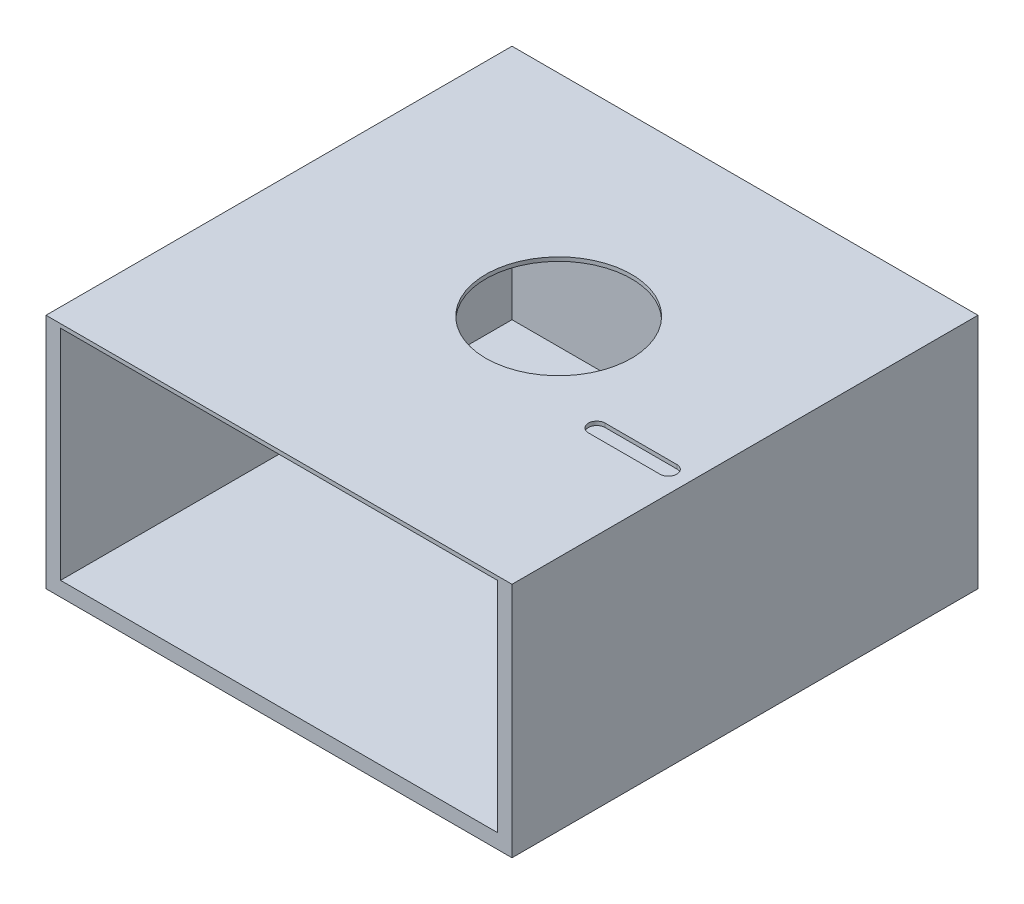
SolidWorks part; units mm, degrees
ref_plane "Front Plane" through (0, 0, 0) normal (0, 0, 1) x (1, 0, 0)
ref_plane "Top Plane" through (0, 0, 0) normal (0, 1, 0) x (1, 0, 0)
ref_plane "Right Plane" through (0, 0, 0) normal (1, 0, 0) x (0, 0, -1)
sketch "Sketch1" plane through (0, 0, 0) normal (0, 0, 1) x (1, 0, 0)
  line L1 (-152.4, -76.2) -> (152.4, -76.2)
  line L2 (-152.4, -76.2) -> (-152.4, 76.2)
  line L3 (-152.4, 76.2) -> (152.4, 76.2)
  line L4 (152.4, -76.2) -> (152.4, 76.2)
  line L5 (-152.4, -76.2) -> (152.4, 76.2) construction
  line L6 (-152.4, 76.2) -> (152.4, -76.2) construction
  point P0 (0, 0)
  dimension "D1" = 304.8
  dimension "D2" = 152.4
extrude "Boss-Extrude1" add sketch "Sketch1" along normal blind 304.8
shell "Shell1" thickness 9.525 removed face at (0, 0, 304.8) removed face at (0, 76.2, 152.4)
sketch "Sketch2" plane through (0, 76.2, 0) normal (0, 1, 0) x (1, 0, 0)
  line L0 (-142.875, -304.8) -> (142.875, -304.8)
  line L8 (-152.4, -304.8) -> (-142.875, -304.8)
  line L9 (-142.875, -304.8) -> (-142.875, -9.525)
  line L10 (-142.875, -9.525) -> (142.875, -9.525)
  line L11 (142.875, -9.525) -> (142.875, -304.8)
  line L12 (142.875, -304.8) -> (152.4, -304.8)
  line L13 (152.4, -304.8) -> (152.4, 0)
  line L14 (152.4, 0) -> (-152.4, 0)
  line L15 (-152.4, 0) -> (-152.4, -304.8)
  line L16 (-152.4, -304.8) -> (-142.875, -304.8)
  line L20 (142.875, -304.8) -> (152.4, -304.8)
  line L21 (152.4, -304.8) -> (152.4, 0)
  line L22 (152.4, 0) -> (-152.4, 0)
  line L23 (-152.4, 0) -> (-152.4, -304.8)
  dimension "D1" = 0
extrude "Boss-Extrude2" add sketch "Sketch2" along normal blind 2.54
sketch "Sketch3" plane through (0, 78.74, 0) normal (0, 1, 0) x (1, 0, 0)
  line L10 (15.875, -108.3347) -> (-28.9142, -140.876)
  line L11 (-28.9142, -140.876) -> (-11.8063, -193.5289)
  line L12 (-11.8063, -193.5289) -> (43.5563, -193.5289)
  line L13 (43.5563, -193.5289) -> (60.6642, -140.876)
  line L14 (60.6642, -140.876) -> (15.875, -108.3347)
  circle A1 centre (15.875, -155.4289) radius 3.175
sketch "Sketch4" plane through (0, 78.74, 0) normal (0, 1, 0) x (1, 0, 0)
  circle A1 centre (15.875, -137.7401) radius 47.625
  dimension "D1" = 95.25
extrude "Cut-Extrude1" cut sketch "Sketch4" against normal blind 7.62
sketch "Sketch5" plane through (0, 78.74, 0) normal (0, 1, 0) x (1, 0, 0)
  line L2 (89.7396, -162.406) -> (138.9776, -162.406)
  line L3 (138.9776, -156.056) -> (89.7396, -156.056)
  ellipse E1 centre (138.9776, -159.231) end of major axis (138.9776, -156.056) minor radius 3.0047
sketch "Sketch6" plane through (0, 78.74, 0) normal (0, 1, 0) x (1, 0, 0)
  line L0 (138.9776, -159.231) -> (95.0898, -159.231) construction
  line L1 (138.9776, -163.5234) -> (95.0898, -163.5234)
  line L2 (138.9776, -154.9386) -> (95.0898, -154.9386)
  arc A0 (138.9776, -163.5234) -> (138.9776, -154.9386) centre (138.9776, -159.231) ccw
  arc A1 (95.0898, -154.9386) -> (95.0898, -163.5234) centre (95.0898, -159.231) ccw
  point P3 (117.0337, -159.231)
extrude "Cut-Extrude2" [suppressed] cut sketch "Sketch6" against normal blind 2.54
sketch "Sketch8" plane through (0, 78.74, 0) normal (0, 1, 0) x (1, 0, 0)
  line L1 (138.4375, -185.3651) -> (89.5629, -185.3651)
  line L4 (-152.4, 0) -> (-152.4, -304.8)
  line L5 (-152.4, -304.8) -> (152.4, -304.8)
  line L6 (152.4, -304.8) -> (152.4, 0)
  line L7 (152.4, 0) -> (-152.4, 0)
  line L8 (-152.4, 0) -> (-152.4, -304.8)
  line L9 (-152.4, -304.8) -> (152.4, -304.8)
  line L10 (152.4, -304.8) -> (152.4, 0)
  line L11 (152.4, 0) -> (-152.4, 0)
  ellipse E2 centre (138.4375, -188.5401) end of major axis (138.4375, -185.3651) minor radius 3.0073
  dimension "D1" = 0
sketch "Sketch9" plane through (0, 78.74, 0) normal (0, 1, 0) x (1, 0, 0)
  line L0 (138.4375, -188.5401) -> (91.5808, -188.5401) construction
  line L1 (138.4375, -194.05) -> (91.5808, -194.05)
  line L2 (138.4375, -183.0302) -> (91.5808, -183.0302)
  arc A0 (138.4375, -194.05) -> (138.4375, -183.0302) centre (138.4375, -188.5401) ccw
  arc A1 (91.5808, -183.0302) -> (91.5808, -194.05) centre (91.5808, -188.5401) ccw
  point P3 (115.0091, -188.5401)
extrude "Cut-Extrude3" cut sketch "Sketch9" against normal blind 2.54
